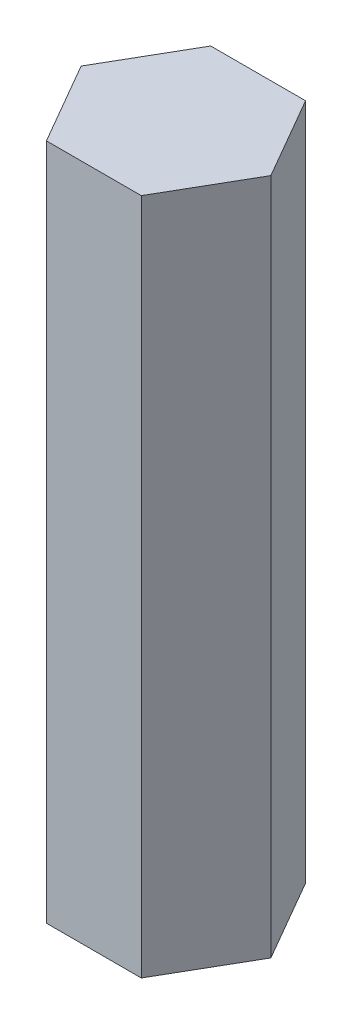
SolidWorks part; units mm, degrees
ref_plane "前视基准面" through (0, 0, 0) normal (0, 0, 1) x (1, 0, 0)
ref_plane "上视基准面" through (0, 0, 0) normal (0, 1, 0) x (1, 0, 0)
ref_plane "右视基准面" through (0, 0, 0) normal (1, 0, 0) x (0, 0, -1)
other "Configuration Table"
sketch "草图1" plane through (0, 0, 0) normal (0, 1, 0) x (1, 0, 0)
  line L1 (700, 0) -> (350, 606.2178)
  line L2 (350, 606.2178) -> (-350, 606.2178)
  line L3 (-350, 606.2178) -> (-700, 0)
  line L4 (-700, 0) -> (-350, -606.2178)
  line L5 (-350, -606.2178) -> (350, -606.2178)
  line L6 (350, -606.2178) -> (700, 0)
  circle A0 centre (0, 0) radius 606.2178 construction
extrude "凸台-拉伸1" add sketch "草图1" along normal blind 5000
ref_point "点2"
sketch "草图2" plane through (-525, 0, -303.1089) normal (-0.866, 0, -0.5) x (-0.5, 0, 0.866)
  line L0 (0, 2500) -> (-250, 2500)
ref_point "点4"
ref_point "点6"
ref_point "点8"
sketch "草图3" plane through (0, 0, -606.2178) normal (0, 0, -1) x (-1, 0, 0)
  line L0 (0, 2500) -> (-200, 2500)
ref_point "点10"
ref_axis "基准轴1" through (200, 2500, -606.2178) along (0, 0, -1)
ref_axis "基准轴2" through (0, 2500, -606.2178) along (1, 0, 0)
